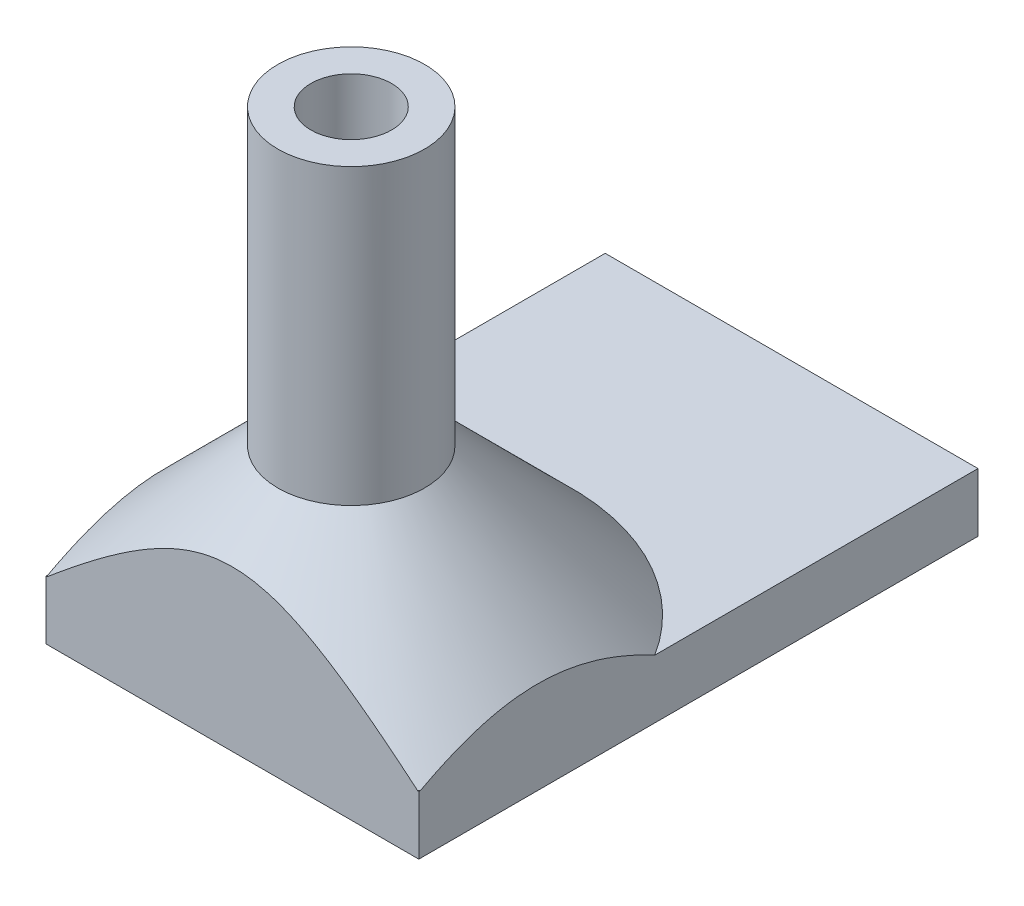
SolidWorks part; units mm, degrees
ref_plane "Front Plane" through (0, 0, 0) normal (0, 0, 1) x (1, 0, 0)
ref_plane "Top Plane" through (0, 0, 0) normal (0, 1, 0) x (1, 0, 0)
ref_plane "Right Plane" through (0, 0, 0) normal (1, 0, 0) x (0, 0, -1)
sketch "Sketch1" plane through (0, 0, 0) normal (0, 1, 0) x (1, 0, 0)
  line L1 (-12.7, 19.05) -> (12.7, 19.05)
  line L2 (-12.7, 19.05) -> (-12.7, -19.05)
  line L3 (-12.7, -19.05) -> (12.7, -19.05)
  line L4 (12.7, 19.05) -> (12.7, -19.05)
  line L5 (-12.7, 19.05) -> (12.7, -19.05) construction
  line L6 (-12.7, -19.05) -> (12.7, 19.05) construction
  point P0 (0, 0)
  dimension "D1" = 25.4
  dimension "D2" = 38.1
extrude "Boss-Extrude1" add sketch "Sketch1" along normal blind 4
sketch "Sketch2" plane through (0, 4, 0) normal (0, 1, 0) x (1, 0, 0)
  circle A0 centre (0, -10.9532) radius 5
  dimension "D1" = 10
extrude "Boss-Extrude2" add sketch "Sketch2" along normal blind 30
sketch "Sketch3" plane through (0, 34, 0) normal (0, 1, 0) x (1, 0, 0)
  circle A0 centre (0, -10.9532) radius 2.75
  dimension "D1" = 5.5
extrude "Cut-Extrude1" cut sketch "Sketch3" against normal blind 40
chamfer "Chamfer1" distance 10 angle 45 1 edges at (0, 4, 15.9532)
